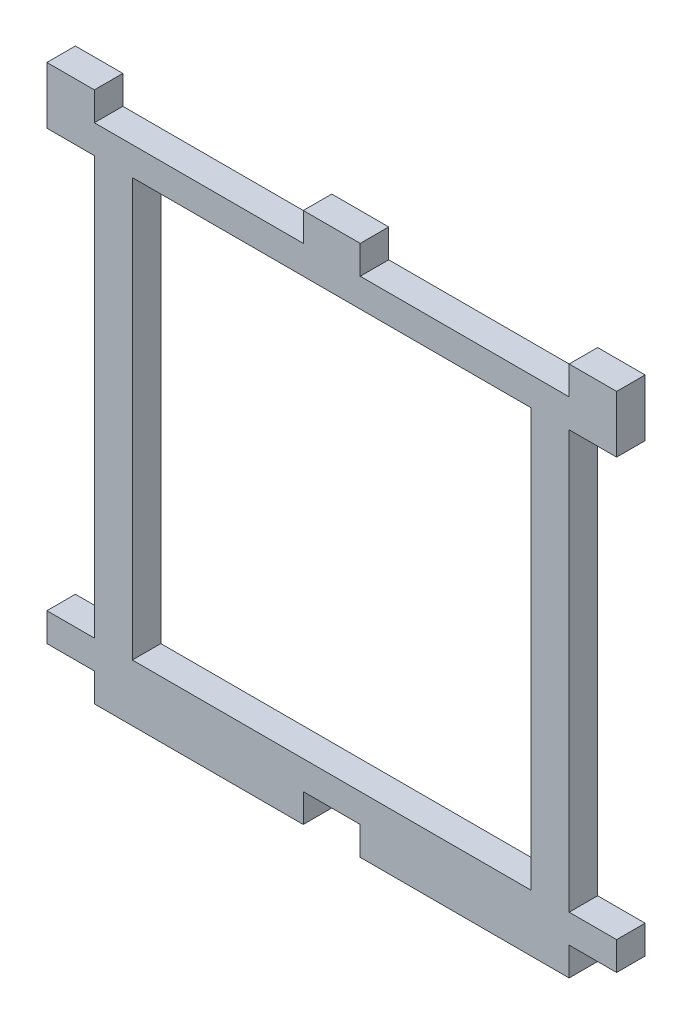
SolidWorks part; units mm, degrees
material "Custom Plastic"
ref_plane "Front Plane" through (0, 0, 0) normal (0, 0, 1) x (1, 0, 0)
ref_plane "Top Plane" through (0, 0, 0) normal (0, 1, 0) x (1, 0, 0)
ref_plane "Right Plane" through (0, 0, 0) normal (1, 0, 0) x (0, 0, -1)
sketch "Sketch1" plane through (0, 0, 0) normal (0, 0, 1) x (1, 0, 0)
  line L0 (-41.2824, 35.9958) -> (-36.2824, 35.9958)
  line L1 (-36.2824, 35.9958) -> (-36.2824, -8.0042)
  line L2 (-36.2824, -8.0042) -> (-41.2824, -8.0042)
  line L3 (-41.2824, -8.0042) -> (-41.2824, -11.0042)
  line L4 (-41.2824, -11.0042) -> (-36.2824, -11.0042)
  line L5 (-36.2824, -11.0042) -> (-36.2824, -14.0042)
  line L6 (-36.2824, -14.0042) -> (-14.2824, -14.0042)
  line L7 (-14.2824, -14.0042) -> (-14.2824, -11.0042)
  line L8 (-14.2824, -11.0042) -> (-8.2824, -11.0042)
  line L9 (-8.2824, -11.0042) -> (-8.2824, -14.0042)
  line L10 (-8.2824, -14.0042) -> (13.7176, -14.0042)
  line L11 (13.7176, -14.0042) -> (13.7176, -11.0042)
  line L12 (13.7176, -11.0042) -> (18.7176, -11.0042)
  line L13 (18.7176, -11.0042) -> (18.7176, -8.0042)
  line L14 (18.7176, -8.0042) -> (13.7176, -8.0042)
  line L15 (13.7176, -8.0042) -> (13.7176, 35.9958)
  line L16 (13.7176, 35.9958) -> (18.7176, 35.9958)
  line L17 (18.7176, 35.9958) -> (18.7176, 41.9958)
  line L27 (-41.2824, 41.9958) -> (-41.2824, 35.9958)
  line L28 (-36.2824, -8.0042) -> (13.7176, -8.0042) construction
  line L29 (-36.2824, 35.9958) -> (13.7176, 35.9958) construction
  line L30 (-32.2824, -8.0042) -> (-32.2824, 35.9958)
  line L31 (-32.2824, 35.9958) -> (9.7176, 35.9958)
  line L33 (9.7176, -8.0042) -> (-32.2824, -8.0042)
  line L36 (9.7176, 35.9958) -> (9.7176, -8.0042)
  line L37 (-41.2824, 41.9958) -> (-36.2824, 41.9958)
  line L38 (-36.2824, 41.9958) -> (-36.2824, 38.9958)
  line L39 (-36.2824, 38.9958) -> (-14.2824, 38.9958)
  line L40 (-14.2824, 38.9958) -> (-14.2824, 41.9958)
  line L41 (-14.2824, 41.9958) -> (-8.2824, 41.9958)
  line L42 (-8.2824, 41.9958) -> (-8.2824, 38.9958)
  line L43 (-8.2824, 38.9958) -> (13.7176, 38.9958)
  line L44 (13.7176, 38.9958) -> (13.7176, 41.9958)
  line L45 (13.7176, 41.9958) -> (18.7176, 41.9958)
  point P2 (0, 0)
  point P32 (0, 0)
  point P33 (0, 0)
  dimension "D1" = 6
  dimension "D2" = 3
  dimension "D3" = 3
  dimension "D4" = 22
  dimension "D5" = 4
  dimension "D6" = 6
  dimension "D7" = 5
  dimension "D8" = 3
  dimension "D9" = 4
extrude "Boss-Extrude1" add sketch "Sketch1" along normal blind 3
